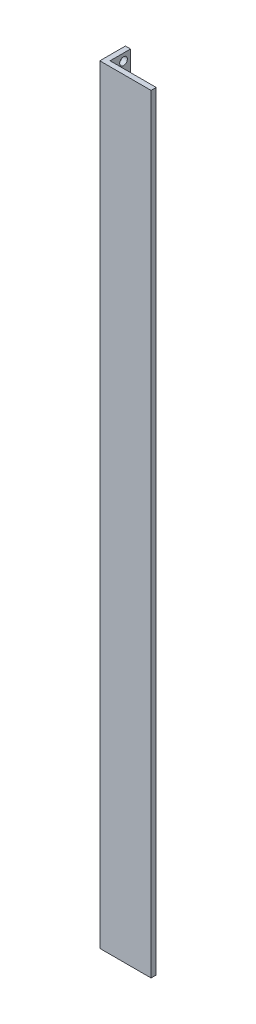
SolidWorks part; units mm, degrees
ref_plane "Front Plane" through (0, 0, 0) normal (0, 0, 1) x (1, 0, 0)
ref_plane "Top Plane" through (0, 0, 0) normal (0, 1, 0) x (1, 0, 0)
ref_plane "Right Plane" through (0, 0, 0) normal (1, 0, 0) x (0, 0, -1)
sketch "Sketch1" plane through (0, 0, 0) normal (0, 1, 0) x (1, 0, 0)
  line L0 (0, 0) -> (0, 10)
  line L1 (0, 10) -> (2, 10)
  line L2 (2, 10) -> (2, 2)
  line L3 (2, 2) -> (20, 2)
  line L4 (20, 2) -> (20, 0)
  line L5 (20, 0) -> (0, 0)
extrude "Boss-Extrude1" add sketch "Sketch1" along normal blind 300
sketch "Sketch2" plane through (0, 0, 0) normal (-1, 0, 0) x (0, 0, 1)
  circle A0 centre (-7.2626, 297.2454) radius 1.5
  circle A1 centre (-7.2585, 88.7434) radius 1.5
extrude "Cut-Extrude1" cut sketch "Sketch2" against normal through all
hole_wizard "Ø3.0 (3) Diameter Hole1" positions "Sketch3" profile "Sketch4" hole size "Ø3.0" standard "ISO" end condition through all
sketch "Sketch3" plane through (2, -25.4076, 52.862) normal (1, 0, 0) x (0, 0, -1)
  point P0 (58.862, 61.4076)
  point P1 (58.862, 37.4076)
sketch "Sketch4" plane through (2, 36, -6) normal (0, 1, 0) x (0, 0, -1)
  line L0 (0, 0) -> (0, 2)
  line L1 (0, 2) -> (1.5, 2)
  line L2 (1.5, 2) -> (1.5, 0)
  line L3 (1.5, 0) -> (0, 0)
  line L4 (0, -6.35) -> (0, 107.95) construction
  dimension "Thru Hole Dia." = 3
  dimension "Thru Hole Depth" = 2
